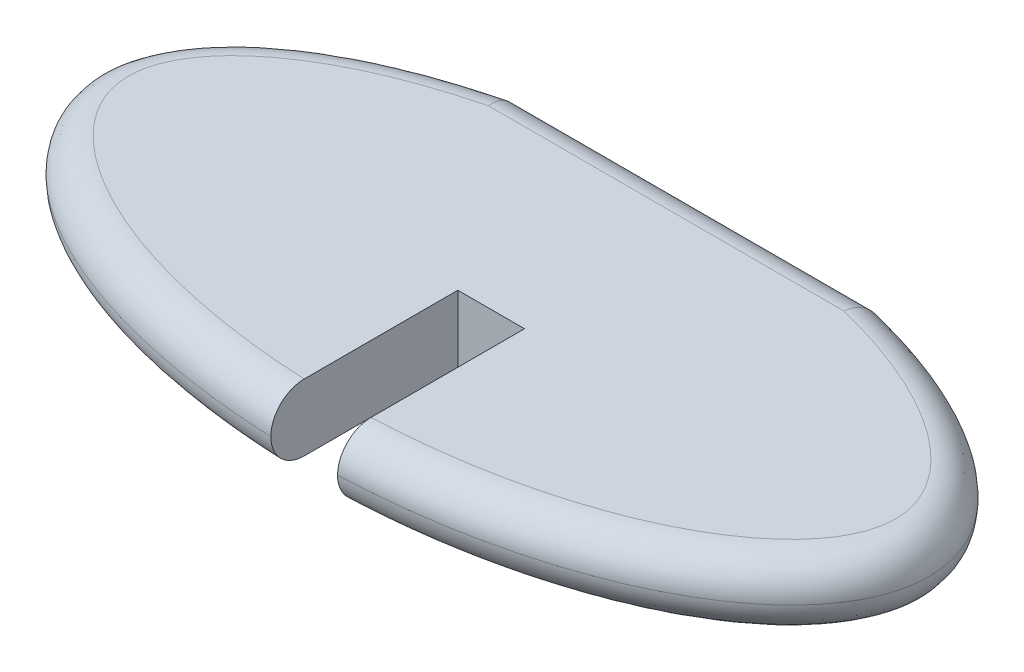
SolidWorks part; units mm, degrees
material "Mahogany"
ref_plane "Front" through (0, 0, 0) normal (0, 0, 1) x (1, 0, 0)
ref_plane "Top" through (0, 0, 0) normal (0, 1, 0) x (1, 0, 0)
ref_plane "Right" through (0, 0, 0) normal (1, 0, 0) x (0, 0, -1)
sketch "Sketch1" plane through (0, 0, 0) normal (0, 1, 0) x (1, 0, 0)
  line L0 (-21.7945, 22.5) -> (21.7945, 22.5)
  ellipse E0 centre (0, 0) end of major axis (-50, 0) minor radius 25
  dimension "D1" = 100
  dimension "D2" = 50
  dimension "D3" = 22.5
extrude "Boss-Extrude1" add sketch "Sketch1" along normal blind 8 contours L0 E0 region at (0, 0, 0.4477)
sketch "Sketch2" plane through (0, 8, 0) normal (0, 1, 0) x (1, 0, 0)
  line L0 (-4, -24.9199) -> (-4, -2.5)
  line L1 (-4, -2.5) -> (4, -2.5)
  line L2 (4, -2.5) -> (4, -24.9199)
  line L4 (-21.7945, 22.5) -> (21.7945, 22.5) construction
  ellipse E0 centre (0, 0) end of major axis (-50, 0) minor radius 25 (-21.7945, 22.5) -> (21.7945, 22.5) ccw construction
  ellipse E1 centre (0, 0) end of major axis (-50, 0) minor radius 25 (-4, -24.9199) -> (4, -24.9199) ccw
  point P14 (0, -2.5)
  dimension "D1" = 25
  dimension "D2" = 8
extrude "Cut-Extrude1" cut sketch "Sketch2" against normal through all
fillet "Fillet1" radius 4 6 edges at (-49.1425, 0, 4.6102) (49.1425, 0, 4.6102) (0, 0, -22.5) (49.1425, 8, 4.6102) (-49.1425, 8, 4.6102) (0, 8, -22.5)
